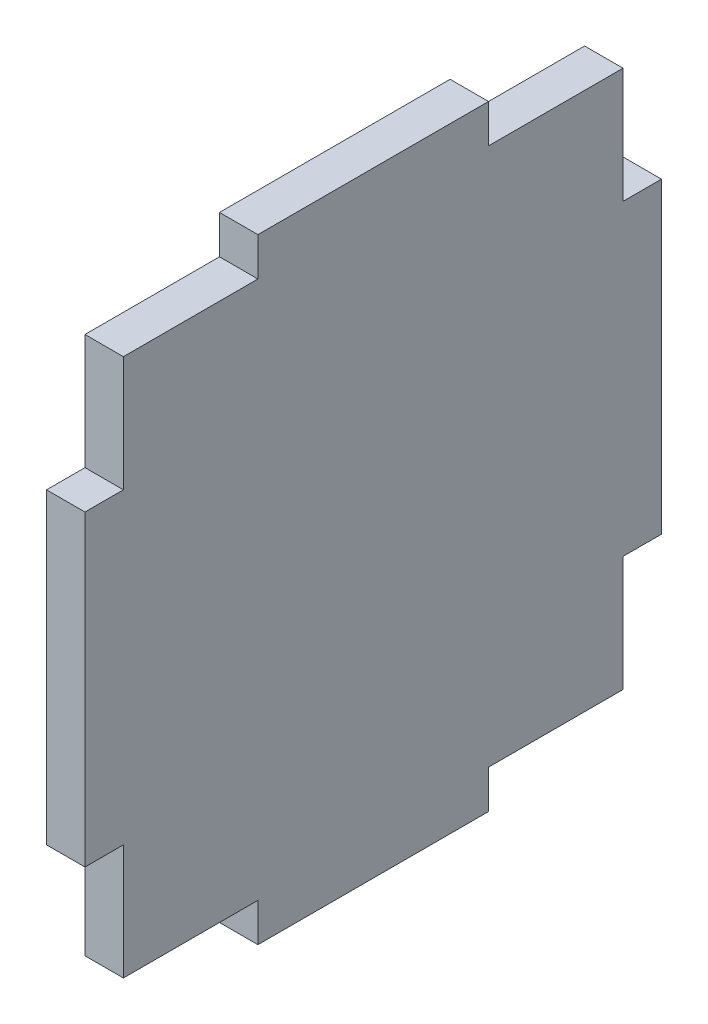
SolidWorks part; units mm, degrees
material "Acrylic (Medium-high impact)"
ref_plane "Front Plane" through (0, 0, 0) normal (0, 0, 1) x (1, 0, 0)
ref_plane "Top Plane" through (0, 0, 0) normal (0, 1, 0) x (1, 0, 0)
ref_plane "Right Plane" through (0, 0, 0) normal (1, 0, 0) x (0, 0, -1)
sketch "Sketch1" plane through (0, 0, 0) normal (1, 0, 0) x (0, 0, -1)
  line L1 (-37.5, -40) -> (37.5, -40)
  line L2 (-37.5, -40) -> (-37.5, 40)
  line L3 (-37.5, 40) -> (37.5, 40)
  line L4 (37.5, -40) -> (37.5, 40)
  line L5 (-37.5, -40) -> (37.5, 40) construction
  line L6 (-37.5, 40) -> (37.5, -40) construction
  point P0 (0, 0)
  dimension "D1" = 75
  dimension "D2" = 80
extrude "Boss-Extrude1" add sketch "Sketch1" along normal blind 5
sketch "Sketch3" plane through (5, 0, 0) normal (1, 0, 0) x (0, 0, -1)
  line L0 (-37.5, 20) -> (-32.5, 20)
  line L1 (-37.5, 40) -> (-37.5, -40) construction
  line L2 (-32.5, 20) -> (-32.5, 35)
  line L3 (-32.5, 35) -> (-15, 35)
  line L4 (-15, 35) -> (-15, 40)
  line L5 (37.5, 40) -> (-37.5, 40) construction
  line L6 (-15, 40) -> (-37.5, 40)
  line L7 (-37.5, 40) -> (-37.5, 20)
  dimension "D1" = 20
  dimension "D2" = 5
  dimension "D3" = 15
extrude "Cut-Extrude1" cut sketch "Sketch3" against normal through all both and the other way through all
mirror "Mirror1" about plane through (0, 0, 0) normal (0, 0, 1) of "Cut-Extrude1" second plane through (0, 0, 0) second plane normal (0, 1, 0)
